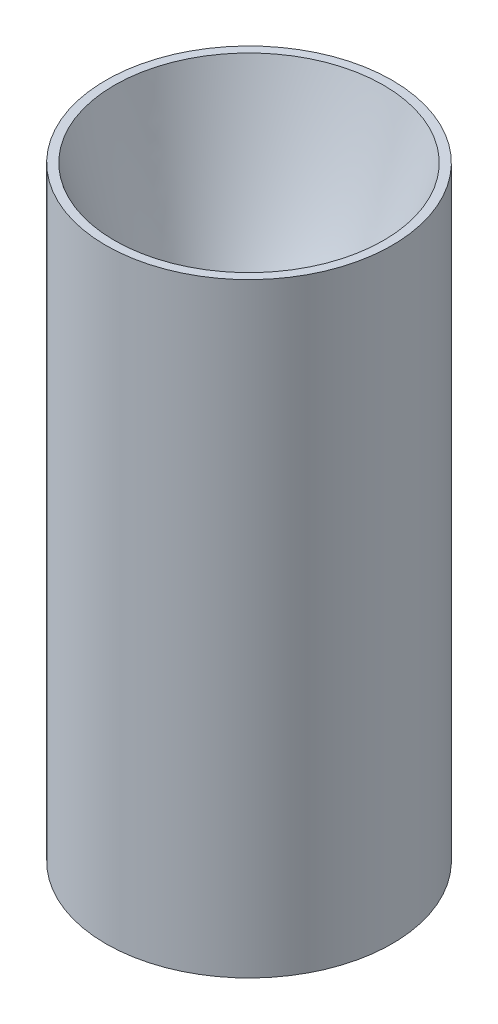
SolidWorks part; units mm, degrees
ref_plane "Front Plane" through (0, 0, 0) normal (0, 0, 1) x (1, 0, 0)
ref_plane "Top Plane" through (0, 0, 0) normal (0, 1, 0) x (1, 0, 0)
ref_plane "Right Plane" through (0, 0, 0) normal (1, 0, 0) x (0, 0, -1)
sketch "Sketch1" plane through (0, 0, 0) normal (0, 0, 1) x (1, 0, 0)
  line L0 (24.01, 0) -> (0, 0) construction
  line L1 (71.6385, 109.9273) -> (76.2, 109.9273)
  line L4 (53.7925, -59.7277) -> (53.7925, -212.1277)
  line L9 (76.2, 109.9273) -> (76.2, -212.1277)
  line L10 (76.2, -212.1277) -> (53.7925, -212.1277)
  line L11 (0, 0) -> (0, -107.6606) construction
  spline S0 degree 2 poles (26.7062, 6.5092) (49.1723, 34.636) (71.6385, 109.9273) knots 0 0 0 1 1 1 construction
  spline S1 degree 2 poles (26.7062, 6.5092) (49.1723, 34.636) (71.6385, 109.9273) knots 0 0 0 1 1 1
  spline S2 degree 4 poles (24.0378, -0.7181) (24.0369, -0.702) (24.0352, -0.674) (24.0319, -0.6548) (24.026, -0.5168) (24.0168, -0.4371) (24.0103, -0.1068) (24.0089, 0.0016) (24.013, 0.2676) (24.0194, 0.4271) (24.0315, 0.6468) (24.0524, 0.9014) (24.0861, 1.2025) (24.1374, 1.5421) (24.2015, 1.881) (24.2781, 2.2164) (24.3673, 2.5492) (24.4687, 2.8781) (24.5826, 3.2033) (24.7081, 3.5236) (24.8462, 3.8397) (24.995, 4.1493) (25.1569, 4.4548) (25.3274, 4.7513) (25.5134, 5.0457) (25.7027, 5.3255) (25.9153, 5.6107) (26.0898, 5.8329) (26.2773, 6.05) (26.4155, 6.2086) (26.6679, 6.4727) (26.7479, 6.5524) (27.0125, 6.8058) (27.099, 6.8781) (27.1963, 6.9666) (27.2147, 6.9802) (27.2373, 7.0002) knots 0 0 0 0 0 0.005192 0.010384 0.020768 0.041536 0.082569 0.102427 0.122284 0.142142 0.162 0.201716 0.241431 0.281147 0.320863 0.360578 0.400294 0.44001 0.479725 0.519441 0.559156 0.598872 0.638588 0.678303 0.718019 0.757735 0.79745 0.837166 0.857024 0.876882 0.916597 0.958047 0.979024 0.989512 1 1 1 1 1 construction
  spline S3 degree 4 poles (24.01, 0) (24.01, 0.0359) (24.0105, 0.1101) (24.013, 0.2676) (24.0194, 0.4271) (24.0315, 0.6468) (24.0524, 0.9014) (24.0861, 1.2025) (24.1374, 1.5421) (24.2015, 1.881) (24.2781, 2.2164) (24.3673, 2.5492) (24.4687, 2.8781) (24.5826, 3.2033) (24.7081, 3.5236) (24.8462, 3.8397) (24.995, 4.1493) (25.1569, 4.4548) (25.3274, 4.7513) (25.5134, 5.0457) (25.7027, 5.3255) (25.9153, 5.6107) (26.0898, 5.8329) (26.2773, 6.05) (26.4155, 6.2086) (26.5814, 6.3821) (26.6555, 6.4585) (26.7062, 6.5092) knots 0.082569 0.082569 0.082569 0.082569 0.082569 0.102427 0.122284 0.142142 0.162 0.201716 0.241431 0.281147 0.320863 0.360578 0.400294 0.44001 0.479725 0.519441 0.559156 0.598872 0.638588 0.678303 0.718019 0.757735 0.79745 0.837166 0.857024 0.876882 0.916597 0.916597 0.916597 0.916597 0.916597
  spline S4 degree 4 poles (24.1192, 2.8078) (24.1123, 2.7164) (24.0991, 2.5516) (24.0751, 2.1752) (24.0462, 1.6879) (24.0258, 1.1016) (24.0139, 0.6554) (24.0097, 0.1102) (24.0097, -0.1001) (24.0129, -0.5432) (24.0192, -0.8242) (24.0287, -1.1948) (24.0414, -1.5134) (24.0572, -1.8619) (24.0761, -2.1937) (24.1038, -2.6181) (24.1432, -3.122) (24.2142, -3.88) (24.3341, -4.8865) (24.5104, -6.0567) (24.7618, -7.3852) (25.0627, -8.7036) (25.4127, -10.0096) (25.8113, -11.3018) (26.2579, -12.5781) (26.7519, -13.8369) (27.2926, -15.0762) (27.8794, -16.2946) (28.5111, -17.4899) (29.1875, -18.6613) (29.9064, -19.8057) (30.669, -20.9239) (31.3701, -21.8744) (31.9997, -22.6734) (32.5351, -23.3204) (32.9832, -23.84) (33.4194, -24.3298) (33.8468, -24.7885) (34.1565, -25.1139) (34.523, -25.486) (34.677, -25.64) (35.0618, -26.0189) (35.3885, -26.3288) (35.8159, -26.7274) (36.1505, -27.0244) (36.4301, -27.2709) (36.5574, -27.38) (36.6257, -27.4388) (36.6605, -27.4687) knots 0 0 0 0 0 0.010393 0.020785 0.041571 0.062104 0.072371 0.082638 0.092575 0.102512 0.112449 0.122387 0.132324 0.142261 0.152198 0.162135 0.18201 0.201884 0.241633 0.281382 0.32113 0.360879 0.400628 0.440377 0.480126 0.519874 0.559623 0.599372 0.639121 0.67887 0.718618 0.758367 0.798116 0.81799 0.837865 0.857739 0.877613 0.897488 0.907425 0.917362 0.927629 0.937896 0.958429 0.979215 0.989607 0.994804 1 1 1 1 1 construction
  spline S5 degree 4 poles (24.01, 0) (24.01, -0.0705) (24.0105, -0.2136) (24.0129, -0.5432) (24.0192, -0.8242) (24.0287, -1.1948) (24.0414, -1.5134) (24.0572, -1.8619) (24.0761, -2.1937) (24.1038, -2.6181) (24.1432, -3.122) (24.2142, -3.88) (24.3341, -4.8865) (24.5104, -6.0567) (24.7618, -7.3852) (25.0627, -8.7036) (25.4127, -10.0096) (25.8113, -11.3018) (26.2579, -12.5781) (26.7519, -13.8369) (27.2926, -15.0762) (27.8794, -16.2946) (28.5111, -17.4899) (29.1875, -18.6613) (29.9064, -19.8057) (30.669, -20.9239) (31.3701, -21.8744) (31.9997, -22.6734) (32.5351, -23.3204) (32.9832, -23.84) (33.4194, -24.3298) (33.8468, -24.7885) (34.1565, -25.1139) (34.4478, -25.4096) (34.5473, -25.5099) (34.5972, -25.5598) knots 0.082638 0.082638 0.082638 0.082638 0.082638 0.092575 0.102512 0.112449 0.122387 0.132324 0.142261 0.152198 0.162135 0.18201 0.201884 0.241633 0.281382 0.32113 0.360879 0.400628 0.440377 0.480126 0.519874 0.559623 0.599372 0.639121 0.67887 0.718618 0.758367 0.798116 0.81799 0.837865 0.857739 0.877613 0.897488 0.907425 0.917362 0.917362 0.917362 0.917362 0.917362
  spline S6 degree 1 poles (34.5972, -25.5598) (43.2048, -34.1675) knots 0 0 1 1 construction
  spline S7 degree 1 poles (34.5972, -25.5598) (43.2048, -34.1675) knots 0 0 1 1
  spline S8 degree 4 poles (53.6833, -62.5354) (53.6902, -62.4466) (53.7033, -62.2738) (53.7213, -62.0018) (53.7419, -61.6601) (53.7589, -61.2922) (53.7725, -60.9659) (53.7826, -60.5754) (53.7894, -60.2941) (53.7927, -59.8333) (53.7927, -59.6305) (53.7896, -59.1817) (53.7832, -58.905) (53.7737, -58.5327) (53.7611, -58.213) (53.7414, -57.7818) (53.7113, -57.2811) (53.6671, -56.6882) (53.5882, -55.8486) (53.4884, -55.0083) (53.3676, -54.1726) (53.1977, -53.1726) (53.003, -52.1776) (52.7773, -51.1887) (52.5209, -50.2076) (52.2402, -49.2332) (51.9353, -48.2661) (51.5445, -47.1493) (51.0505, -45.8906) (50.5097, -44.6511) (49.923, -43.4329) (49.2911, -42.2373) (48.6151, -41.0663) (47.8954, -39.9211) (47.134, -38.8042) (46.4308, -37.8516) (45.8045, -37.0558) (45.2637, -36.4035) (44.8261, -35.8944) (44.4257, -35.4472) (44.0924, -35.0848) (43.7849, -34.7605) (43.585, -34.5517) (43.2762, -34.2384) (43.1268, -34.0891) (42.7386, -33.7068) (42.415, -33.3999) (41.985, -32.9988) (41.6521, -32.7035) (41.3716, -32.4561) (41.2447, -32.3474) (41.1763, -32.2885) (41.1415, -32.2585) knots 0 0 0 0 0 0.010393 0.020785 0.031178 0.041571 0.051838 0.062104 0.072371 0.082638 0.092575 0.102512 0.112449 0.122387 0.132324 0.142261 0.162135 0.18201 0.201884 0.241633 0.261507 0.281382 0.32113 0.360879 0.380754 0.400628 0.440377 0.480126 0.519874 0.559623 0.599372 0.639121 0.67887 0.718618 0.758367 0.798116 0.81799 0.837865 0.857739 0.877613 0.887551 0.897488 0.907425 0.917362 0.927629 0.937896 0.958429 0.979215 0.989607 0.994804 1 1 1 1 1 construction
  spline S9 degree 4 poles (53.7925, -59.7277) (53.7925, -59.6571) (53.7919, -59.5156) (53.7896, -59.1817) (53.7832, -58.905) (53.7737, -58.5327) (53.7611, -58.213) (53.7414, -57.7818) (53.7113, -57.2811) (53.6671, -56.6882) (53.5882, -55.8486) (53.4884, -55.0083) (53.3676, -54.1726) (53.1977, -53.1726) (53.003, -52.1776) (52.7773, -51.1887) (52.5209, -50.2076) (52.2402, -49.2332) (51.9353, -48.2661) (51.5445, -47.1493) (51.0505, -45.8906) (50.5097, -44.6511) (49.923, -43.4329) (49.2911, -42.2373) (48.6151, -41.0663) (47.8954, -39.9211) (47.134, -38.8042) (46.4308, -37.8516) (45.8045, -37.0558) (45.2637, -36.4035) (44.8261, -35.8944) (44.4257, -35.4472) (44.0924, -35.0848) (43.7849, -34.7605) (43.585, -34.5517) (43.3553, -34.3187) (43.2547, -34.2173) (43.2048, -34.1675) knots 0.082638 0.082638 0.082638 0.082638 0.082638 0.092575 0.102512 0.112449 0.122387 0.132324 0.142261 0.162135 0.18201 0.201884 0.241633 0.261507 0.281382 0.32113 0.360879 0.380754 0.400628 0.440377 0.480126 0.519874 0.559623 0.599372 0.639121 0.67887 0.718618 0.758367 0.798116 0.81799 0.837865 0.857739 0.877613 0.887551 0.897488 0.907425 0.917362 0.917362 0.917362 0.917362 0.917362
  spline S10 degree 2 poles (36.8348, 6.4922) (58.583, 46.9283) (81.7275, 109.9275) knots 0.437765 0.437765 0.437765 0.998349 0.998349 0.998349 construction
  dimension "D1" = 152.4
  dimension "D2" = 24.01
  dimension "D3" = 152.4
revolve "Revolve2" add sketch "Sketch1" angle 360 about L11
hole_wizard "3/8-24 Tapped Hole1" positions "Sketch3" profile "Sketch4" tap size "3/8-24" standard "ANSI Inch"
sketch "Sketch3" plane through (0, -212.1277, 0) normal (0, -1, 0) x (-1, 0, 0)
  circle A1 centre (0, 0) radius 65.2 construction
  point P10 (-65.2, 0)
  dimension "D1" = 130.4
sketch "Sketch4" plane through (65.2, -212.1277, 0) normal (1, 0, 0) x (0, 0, -1)
  line L0 (0, 0) -> (0, 27.5335)
  line L1 (0, 27.5335) -> (4.2164, 25)
  line L2 (4.2164, 25) -> (4.2164, 0)
  line L5 (4.2164, 0) -> (0, 0)
  line L10 (0, 27.5335) -> (-4.2164, 25) construction
  line L11 (0, -6.35) -> (0, 107.95) construction
  dimension "Tap Drill Dia." = 8.4328
  dimension "Tap Drill Depth" = 25
  dimension "Drill Angle" = 118
cosmetic thread "Hole Thread1" parameters "D1"=20, "D2"=9.525
pattern_circular "CirPattern1" count 8 over 360 about axis through (0, -212.1277, 0) along (0, 1, 0) of "3/8-24 Tapped Hole1"
cosmetic thread "Hole Thread2" parameters "D1"=20, "D2"=9.525
cosmetic thread "Hole Thread3" parameters "D1"=20, "D2"=9.525
cosmetic thread "Hole Thread4" parameters "D1"=20, "D2"=9.525
cosmetic thread "Hole Thread5" parameters "D1"=20, "D2"=9.525
cosmetic thread "Hole Thread6" parameters "D1"=20, "D2"=9.525
cosmetic thread "Hole Thread7" parameters "D1"=20, "D2"=9.525
cosmetic thread "Hole Thread8" parameters "D1"=20, "D2"=9.525
sketch "Sketch8" [suppressed] plane through (0, -212.1275, 0) normal (0, -1, 0) x (1, 0, 0)
  circle A0 centre (0, 0) radius 53.8815 construction
  circle A1 centre (0, 0) radius 76.49 construction
  circle A2 centre (0, 0) radius 65.2002 construction
  dimension "D1" = 107.7631
  dimension "D2" = 130.4004
  dimension "D3" = 152.98
sketch "Sketch9" plane through (0, -212.1277, 0) normal (0, -1, 0) x (1, 0, 0)
  circle A0 centre (0, 0) radius 53.8815
  circle A1 centre (0, 0) radius 56.8815
  dimension "D1" = 3
extrude "Cut-Extrude1" [suppressed] cut sketch "Sketch9" against normal blind 6
hole_wizard "1/4 (0.2500) Dowel Hole1" positions "Sketch11" profile "Sketch12" hole size "1/4" standard "ANSI Inch"
sketch "Sketch11" plane through (0, -212.1277, 0) normal (0, -1, 0) x (-1, 0, 0)
  line L6 (0, 0) -> (60.2369, -24.951) construction
  line L8 (0, 0) -> (-60.2369, 24.951) construction
  line L9 (0, 0) -> (-65.2, 0) construction
  circle A0 centre (0, 0) radius 65.2 construction
  point P22 (60.2369, -24.951)
  point P28 (-60.2369, 24.951)
  dimension "D1" = 22.5
sketch "Sketch12" plane through (60.2369, -212.1277, -24.951) normal (1, 0, 0) x (0, 0, -1)
  line L0 (0, 0) -> (0, 11.8137)
  line L1 (0, 11.8137) -> (3.175, 9.906)
  line L2 (3.175, 9.906) -> (3.175, 0)
  line L5 (3.175, 0) -> (0, 0)
  line L10 (0, 11.8137) -> (-3.175, 9.906) construction
  line L11 (0, -6.35) -> (0, 107.95) construction
  dimension "Hole Dia." = 6.35
  dimension "Hole Depth" = 9.906
  dimension "Drill Angle" = 118
